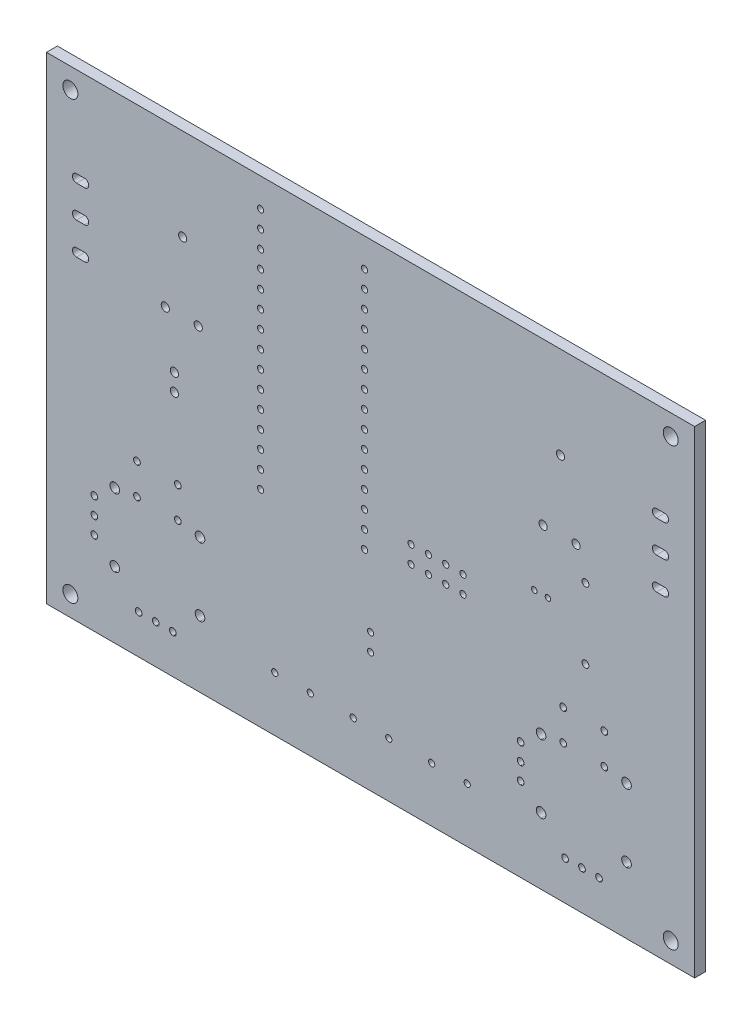
SolidWorks part; units mm, degrees
material "Copper"
ref_plane "Front" through (0, 0, 0) normal (0, 0, 1) x (1, 0, 0)
ref_plane "Top" through (0, 0, 0) normal (0, 1, 0) x (1, 0, 0)
ref_plane "Right" through (0, 0, 0) normal (1, 0, 0) x (0, 0, -1)
sketch "Sketch1" plane through (0, 0, 0) normal (0, 0, 1) x (1, 0, 0)
  line B0 (0, 70) -> (0, 0)
  circle B1 centre (19.9601, 56.5399) radius 1.08
  circle B2 centre (31.38, 60.7) radius 0.4572
  circle B3 centre (31.3799, 60.6999) radius 0.762
  circle B4 centre (31.38, 58.16) radius 0.4572
  circle B5 centre (17.42, 46.38) radius 0.6
  circle B6 centre (17.4201, 46.3799) radius 1.08
  line B7 (95, 70) -> (0, 70)
  line B8 (0, 0) -> (95, 0)
  line B9 (95, 0) -> (95, 70)
  line B10 (6, 57.2) -> (4, 57.2)
  line B11 (4, 57.2) -> (6, 57.2)
  line B12 (6, 55.2) -> (4, 55.2)
  line B13 (4, 55.2) -> (6, 55.2)
  line B14 (5.6, 56.8) -> (4.4, 56.8)
  line B15 (4.4, 56.8) -> (5.6, 56.8)
  line B16 (5.6, 55.6) -> (4.4, 55.6)
  line B17 (4.4, 55.6) -> (5.6, 55.6)
  line B18 (6, 52.5) -> (4, 52.5)
  line B19 (4, 52.5) -> (6, 52.5)
  line B20 (6, 50.5) -> (4, 50.5)
  line B21 (4, 50.5) -> (6, 50.5)
  line B22 (5.6, 52.1) -> (4.4, 52.1)
  line B23 (4.4, 52.1) -> (5.6, 52.1)
  line B24 (5.6, 50.9) -> (4.4, 50.9)
  line B25 (4.4, 50.9) -> (5.6, 50.9)
  line B26 (6, 47.8) -> (4, 47.8)
  line B27 (4, 47.8) -> (6, 47.8)
  line B28 (6, 45.8) -> (4, 45.8)
  line B29 (4, 45.8) -> (6, 45.8)
  line B30 (5.6, 47.4) -> (4.4, 47.4)
  line B31 (4.4, 47.4) -> (5.6, 47.4)
  line B32 (5.6, 46.2) -> (4.4, 46.2)
  line B33 (4.4, 46.2) -> (5.6, 46.2)
  line B34 (91.0001, 57.2) -> (89.0001, 57.2)
  line B35 (89.0001, 57.2) -> (91.0001, 57.2)
  line B36 (91.0001, 55.2) -> (89.0001, 55.2)
  line B37 (89.0001, 55.2) -> (91.0001, 55.2)
  line B38 (90.6, 56.8) -> (89.4, 56.8)
  line B39 (89.4, 56.8) -> (90.6, 56.8)
  line B40 (90.6, 55.6) -> (89.4, 55.6)
  line B41 (89.4, 55.6) -> (90.6, 55.6)
  line B42 (91.0001, 52.5) -> (89.0001, 52.5)
  line B43 (89.0001, 52.5) -> (91.0001, 52.5)
  line B44 (91.0001, 50.5) -> (89.0001, 50.5)
  line B45 (89.0001, 50.5) -> (91.0001, 50.5)
  line B46 (90.6, 52.1) -> (89.4, 52.1)
  line B47 (89.4, 52.1) -> (90.6, 52.1)
  line B48 (90.6, 50.9) -> (89.4, 50.9)
  line B49 (89.4, 50.9) -> (90.6, 50.9)
  line B50 (91.0001, 47.8) -> (89.0001, 47.8)
  line B51 (89.0001, 47.8) -> (91.0001, 47.8)
  line B52 (91.0001, 45.8) -> (89.0001, 45.8)
  line B53 (89.0001, 45.8) -> (91.0001, 45.8)
  line B54 (90.6, 47.4) -> (89.4, 47.4)
  line B55 (89.4, 47.4) -> (90.6, 47.4)
  line B56 (90.6, 46.2) -> (89.4, 46.2)
  line B57 (89.4, 46.2) -> (90.6, 46.2)
  line B58 (19.65, 39.67) -> (19.65, 37.87)
  line B59 (19.65, 37.87) -> (17.85, 37.87)
  line B60 (17.85, 37.87) -> (17.85, 39.67)
  line B61 (17.85, 39.67) -> (19.65, 39.67)
  line B62 (52.6907, 32.4793) -> (54.1893, 32.4793)
  line B63 (54.1893, 32.4793) -> (54.1893, 30.9807)
  line B64 (54.1893, 30.9807) -> (52.6907, 30.9807)
  line B65 (52.6907, 30.9807) -> (52.6907, 32.4793)
  circle B66 centre (19.96, 56.54) radius 0.6
  circle B67 centre (22.246, 46.38) radius 0.6
  circle B68 centre (22.2461, 46.3799) radius 1.08
  circle B69 centre (79.0004, 42.1504) radius 0.5
  circle B70 centre (79.0004, 42.1505) radius 0.762
  circle B71 centre (79.0004, 31.8504) radius 0.5
  circle B72 centre (79.0004, 31.8503) radius 0.762
  circle B73 centre (72.795, 46.38) radius 0.6
  circle B74 centre (72.7951, 46.3799) radius 1.08
  circle B75 centre (75.335, 56.54) radius 0.6
  circle B76 centre (75.3351, 56.5399) radius 1.08
  circle B77 centre (77.621, 46.38) radius 0.6
  circle B78 centre (77.6211, 46.3799) radius 1.08
  circle B79 centre (47.498, 20.143) radius 0.45
  circle B80 centre (47.498, 20.1429) radius 0.8255
  circle B81 centre (47.498, 17.603) radius 0.45
  circle B82 centre (47.498, 17.6029) radius 0.8255
  circle B83 centre (18.75, 36.23) radius 0.6
  circle B84 centre (18.75, 36.23) radius 0.9
  circle B85 centre (33.46, 8) radius 0.4572
  circle B86 centre (33.4599, 8) radius 1
  circle B87 centre (38.667, 8) radius 0.4572
  circle B88 centre (38.6669, 8) radius 1
  circle B89 centre (44.96, 8) radius 0.4572
  circle B90 centre (44.96, 8) radius 1
  circle B91 centre (50.167, 8) radius 0.4572
  circle B92 centre (50.167, 8) radius 1
  circle B93 centre (56.46, 8) radius 0.4572
  circle B94 centre (56.4601, 8) radius 1
  circle B95 centre (61.667, 8) radius 0.4572
  circle B96 centre (61.6671, 8) radius 1
  circle B97 centre (71.5, 37.5) radius 0.4
  circle B98 centre (71.5, 37.5) radius 0.65
  circle B99 centre (73.5, 37.5) radius 0.4
  circle B100 centre (73.5, 37.5) radius 0.65
  circle B101 centre (46.62, 30.22) radius 0.4572
  circle B102 centre (46.6199, 30.2199) radius 0.762
  circle B103 centre (46.62, 32.76) radius 0.4572
  circle B104 centre (46.6199, 32.7599) radius 0.762
  circle B105 centre (46.62, 35.3) radius 0.4572
  circle B106 centre (46.6199, 35.2999) radius 0.762
  circle B107 centre (46.62, 37.84) radius 0.4572
  circle B108 centre (46.6199, 37.8399) radius 0.762
  circle B109 centre (46.62, 40.38) radius 0.4572
  circle B110 centre (46.6199, 40.3799) radius 0.762
  circle B111 centre (46.62, 42.92) radius 0.4572
  circle B112 centre (46.6199, 42.9199) radius 0.762
  circle B113 centre (46.62, 45.46) radius 0.4572
  circle B114 centre (46.6199, 45.4599) radius 0.762
  circle B115 centre (46.62, 48) radius 0.4572
  circle B116 centre (46.6199, 47.9999) radius 0.762
  circle B117 centre (46.62, 50.54) radius 0.4572
  circle B118 centre (46.6199, 50.5399) radius 0.762
  circle B119 centre (46.62, 53.08) radius 0.4572
  circle B120 centre (46.6199, 53.0799) radius 0.762
  circle B121 centre (46.62, 55.62) radius 0.4572
  circle B122 centre (46.6199, 55.6199) radius 0.762
  circle B123 centre (46.62, 58.16) radius 0.4572
  circle B124 centre (46.6199, 58.1599) radius 0.762
  circle B125 centre (46.62, 60.7) radius 0.4572
  circle B126 centre (46.6199, 60.6999) radius 0.762
  circle B127 centre (46.62, 63.24) radius 0.4572
  circle B128 centre (46.6199, 63.2399) radius 0.762
  circle B129 centre (46.62, 65.78) radius 0.4572
  circle B130 centre (46.6199, 65.7799) radius 0.762
  circle B131 centre (31.38, 65.78) radius 0.4572
  circle B132 centre (31.3799, 65.7799) radius 0.762
  circle B133 centre (31.38, 63.24) radius 0.4572
  circle B134 centre (31.3799, 63.2399) radius 0.762
  circle B135 centre (31.3799, 58.1599) radius 0.762
  circle B136 centre (31.38, 55.62) radius 0.4572
  circle B137 centre (31.3799, 55.6199) radius 0.762
  circle B138 centre (31.38, 53.08) radius 0.4572
  circle B139 centre (31.3799, 53.0799) radius 0.762
  circle B140 centre (31.38, 50.54) radius 0.4572
  circle B141 centre (31.3799, 50.5399) radius 0.762
  circle B142 centre (31.38, 48) radius 0.4572
  circle B143 centre (31.3799, 47.9999) radius 0.762
  circle B144 centre (31.38, 45.46) radius 0.4572
  circle B145 centre (31.3799, 45.4599) radius 0.762
  circle B146 centre (31.38, 42.92) radius 0.4572
  circle B147 centre (31.3799, 42.9199) radius 0.762
  circle B148 centre (31.38, 40.38) radius 0.4572
  circle B149 centre (31.3799, 40.3799) radius 0.762
  circle B150 centre (31.38, 37.84) radius 0.4572
  circle B151 centre (31.3799, 37.8399) radius 0.762
  circle B152 centre (31.38, 35.3) radius 0.4572
  circle B153 centre (31.3799, 35.2999) radius 0.762
  circle B154 centre (31.38, 32.76) radius 0.4572
  circle B155 centre (31.3799, 32.7599) radius 0.762
  circle B156 centre (31.38, 30.22) radius 0.4572
  circle B157 centre (31.3799, 30.2199) radius 0.762
  circle B158 centre (8.65, 20.3848) radius 0.6985
  circle B159 centre (8.65, 20.3847) radius 1.143
  circle B160 centre (23.89, 20.3848) radius 0.6985
  circle B161 centre (23.89, 20.3847) radius 1.143
  circle B162 centre (23.89, 7.0752) radius 0.6985
  circle B163 centre (23.89, 7.0751) radius 1.143
  circle B164 centre (8.65, 7.0752) radius 0.6985
  circle B165 centre (8.65, 7.0751) radius 1.143
  circle B166 centre (18.81, 3.57) radius 0.4445
  circle B167 centre (18.81, 3.5699) radius 0.889
  circle B168 centre (16.27, 3.57) radius 0.4445
  circle B169 centre (16.27, 3.5699) radius 0.889
  circle B170 centre (13.73, 3.57) radius 0.4445
  circle B171 centre (13.73, 3.5699) radius 0.889
  circle B172 centre (6.11, 13.73) radius 0.4445
  circle B173 centre (6.11, 13.7299) radius 0.889
  circle B174 centre (6.11, 11.19) radius 0.4445
  circle B175 centre (6.11, 11.1899) radius 0.889
  circle B176 centre (6.11, 16.27) radius 0.4445
  circle B177 centre (6.11, 16.2699) radius 0.889
  circle B178 centre (19.445, 21.35) radius 0.4496
  circle B179 centre (19.445, 21.3499) radius 0.889
  circle B180 centre (13.095, 21.35) radius 0.4496
  circle B181 centre (13.095, 21.3499) radius 0.889
  circle B182 centre (13.095, 26.43) radius 0.4496
  circle B183 centre (13.095, 26.4299) radius 0.889
  circle B184 centre (19.445, 26.43) radius 0.4496
  circle B185 centre (19.445, 26.4299) radius 0.889
  circle B186 centre (71.15, 20.3848) radius 0.6985
  circle B187 centre (71.15, 20.3847) radius 1.143
  circle B188 centre (86.39, 20.3848) radius 0.6985
  circle B189 centre (86.39, 20.3847) radius 1.143
  circle B190 centre (86.39, 7.0752) radius 0.6985
  circle B191 centre (86.39, 7.0751) radius 1.143
  circle B192 centre (71.15, 7.0752) radius 0.6985
  circle B193 centre (71.15, 7.0751) radius 1.143
  circle B194 centre (81.31, 3.57) radius 0.4445
  circle B195 centre (81.31, 3.5699) radius 0.889
  circle B196 centre (78.77, 3.57) radius 0.4445
  circle B197 centre (78.77, 3.5699) radius 0.889
  circle B198 centre (76.23, 3.57) radius 0.4445
  circle B199 centre (76.23, 3.5699) radius 0.889
  circle B200 centre (68.61, 13.73) radius 0.4445
  circle B201 centre (68.61, 13.7299) radius 0.889
  circle B202 centre (68.61, 11.19) radius 0.4445
  circle B203 centre (68.61, 11.1899) radius 0.889
  circle B204 centre (68.61, 16.27) radius 0.4445
  circle B205 centre (68.61, 16.2699) radius 0.889
  circle B206 centre (81.945, 21.35) radius 0.4496
  circle B207 centre (81.945, 21.3499) radius 0.889
  circle B208 centre (75.595, 21.35) radius 0.4496
  circle B209 centre (75.595, 21.3499) radius 0.889
  circle B210 centre (75.595, 26.43) radius 0.4496
  circle B211 centre (75.595, 26.4299) radius 0.889
  circle B212 centre (81.945, 26.43) radius 0.4496
  circle B213 centre (81.945, 26.4299) radius 0.889
  circle B214 centre (55.98, 31.73) radius 0.4572
  circle B215 centre (55.9801, 31.7299) radius 0.7493
  circle B216 centre (58.52, 31.73) radius 0.4572
  circle B217 centre (58.5201, 31.7299) radius 0.7493
  circle B218 centre (61.06, 31.73) radius 0.4572
  circle B219 centre (61.0601, 31.7299) radius 0.7493
  circle B220 centre (61.06, 34.27) radius 0.4572
  circle B221 centre (61.0601, 34.2699) radius 0.7493
  circle B222 centre (58.52, 34.27) radius 0.4572
  circle B223 centre (58.5201, 34.2699) radius 0.7493
  circle B224 centre (55.98, 34.27) radius 0.4572
  circle B225 centre (55.9801, 34.2699) radius 0.7493
  circle B226 centre (53.44, 34.27) radius 0.4572
  circle B227 centre (53.4401, 34.2699) radius 0.7493
  arc B228 (4, 57.2) -> (4, 55.2) centre (4, 56.2) ccw
  arc B229 (6, 55.2) -> (6, 57.2) centre (6, 56.2) ccw
  arc B230 (4.4, 56.8) -> (4.4, 55.6) centre (4.4, 56.2) ccw
  arc B231 (5.6, 55.6) -> (5.6, 56.8) centre (5.6, 56.2) ccw
  arc B232 (4, 52.5) -> (4, 50.5) centre (4, 51.5) ccw
  arc B233 (6, 50.5) -> (6, 52.5) centre (6, 51.5) ccw
  arc B234 (4.4, 52.1) -> (4.4, 50.9) centre (4.4, 51.5) ccw
  arc B235 (5.6, 50.9) -> (5.6, 52.1) centre (5.6, 51.5) ccw
  arc B236 (4, 47.8) -> (4, 45.8) centre (4, 46.8) ccw
  arc B237 (6, 45.8) -> (6, 47.8) centre (6, 46.8) ccw
  arc B238 (4.4, 47.4) -> (4.4, 46.2) centre (4.4, 46.8) ccw
  arc B239 (5.6, 46.2) -> (5.6, 47.4) centre (5.6, 46.8) ccw
  arc B240 (89.0001, 57.2) -> (89.0001, 55.2) centre (89.0001, 56.2) ccw
  arc B241 (91.0001, 55.2) -> (91.0001, 57.2) centre (91.0001, 56.2) ccw
  arc B242 (89.4, 56.8) -> (89.4, 55.6) centre (89.4, 56.2) ccw
  arc B243 (90.6, 55.6) -> (90.6, 56.8) centre (90.6, 56.2) ccw
  arc B244 (89.0001, 52.5) -> (89.0001, 50.5) centre (89.0001, 51.5) ccw
  arc B245 (91.0001, 50.5) -> (91.0001, 52.5) centre (91.0001, 51.5) ccw
  arc B246 (89.4, 52.1) -> (89.4, 50.9) centre (89.4, 51.5) ccw
  arc B247 (90.6, 50.9) -> (90.6, 52.1) centre (90.6, 51.5) ccw
  arc B248 (89.0001, 47.8) -> (89.0001, 45.8) centre (89.0001, 46.8) ccw
  arc B249 (91.0001, 45.8) -> (91.0001, 47.8) centre (91.0001, 46.8) ccw
  arc B250 (89.4, 47.4) -> (89.4, 46.2) centre (89.4, 46.8) ccw
  arc B251 (90.6, 46.2) -> (90.6, 47.4) centre (90.6, 46.8) ccw
  circle B252 centre (18.75, 38.77) radius 0.6
  circle B253 centre (53.44, 31.73) radius 0.4572
  circle B254 centre (3.5001, 3) radius 1.1
  circle B255 centre (91.4999, 3) radius 1.1
  circle B256 centre (91.4999, 66.9998) radius 1.1
  circle B257 centre (3.5001, 66.9998) radius 1.1
sketch_block_instance "based-1"
sketch_block "based"
extrude "Boss-Extrude1" add sketch "Sketch1" along normal mid plane 1.6 contours B9 B7 B0 B8 B257 B256 B255 B254 B249 B52 B248 B50 B245 B44 B244 B42 B241 B36 B240 B34 B237 B28 B236 B26 B233 B20 B232 B18 B229 B12 B228 B10 B227 B225 B223 B221 | B12 B229 B10 B228 B231 B16 B230 B14 | B20 B233 B18 B232 B235 B24 B234 B22 | B28 B237 B26 B236 B239 B32 B238 B30 | B1 B66 | B6 B5 | B68 B67 | B61 B60 B59 B58 B252 | B84 B83 | B183 B182 | B185 B184 | B179 B178 | B181 B180 | B159 B158 | B161 B160 | B173 B172 | B175 B174 | B177 B176 | B165 B164 | B171 B170 | B169 B168 | B167 B166 | B163 B162 | B86 B85 | B88 B87 | B90 B89 | B92 B91 | B96 B95 | B94 B93 | B193 B192 | B203 B202 | B201 B200 | B205 B204 | B199 B198 | B197 B196 | B195 B194 | B191 B190 | B207 B206 | B189 B188 | B187 B186 | B209 B208 | B211 B210 | B213 B212 | B72 B71 | B100 B99 | B98 B97 | B78 B77 | B74 B73 | B70 B69 | B52 B249 B50 B248 B251 B56 B250 B54 | B44 B245 B42 B244 B247 B48 B246 B46 | B36 B241 B34 B240 B243 B40 B242 B38 | B76 B75 | B80 B79 | B82 B81 | B223 B222 | B217 B216 | B215 B214 | B219 B218 | B65 B64 B63 B62 B253 | B225 B224 | B227 B226 | B102 B101 | B104 B103 | B106 B105 | B108 B107 | B110 B109 | B112 B111 | B114 B113 | B116 B115 | B118 B117 | B122 B121 | B120 B119 | B124 B123 | B126 B125 | B128 B127 | B130 B129 | B132 B131 | B135 B4 | B3 B2 | B134 B133 | B137 B136 | B141 B140 | B139 B138 | B143 B142 | B145 B144 | B149 B148 | B147 B146 | B151 B150 | B153 B152 | B155 B154 | B157 B156 | B221 B220 | B158 | B176 | B172 | B174 | B164 | B162 | B178 | B180 | B160 | B182 | B184 | B166 | B168 | B170 | B188 | B186 | B208 | B206 | B212 | B210 | B204 | B200 | B202 | B192 | B198 | B194 | B196 | B190 region at (47.5716, 35.0845, 0) region at (18.9106, 56.5399, 0) region at (30.6395, 60.6999, 0) region at (16.3706, 46.3799, 0) region at (6.9553, 56.2, 0) region at (6.9553, 51.5, 0) region at (6.9553, 46.8, 0) region at (91.9553, 56.2, 0) region at (91.9553, 51.5, 0) region at (91.9553, 46.8, 0) region at (19.6245, 38.77, 0) region at (53.44, 32.4581, 0) region at (21.1966, 46.3799, 0) region at (78.2599, 42.1505, 0) region at (78.2599, 31.8503, 0) region at (71.7457, 46.3799, 0) region at (74.2857, 56.5399, 0) region at (76.5717, 46.3799, 0) region at (46.6958, 20.1429, 0) region at (46.6958, 17.6029, 0) region at (17.8755, 36.23, 0) region at (32.4882, 8, 0) region at (37.6952, 8, 0) region at (43.9883, 8, 0) region at (49.1953, 8, 0) region at (55.4884, 8, 0) region at (60.6954, 8, 0) region at (70.8684, 37.5, 0) region at (72.8684, 37.5, 0) region at (45.8795, 30.2199, 0) region at (45.8795, 32.7599, 0) region at (45.8795, 35.2999, 0) region at (45.8795, 37.8399, 0) region at (45.8795, 40.3799, 0) region at (45.8795, 42.9199, 0) region at (45.8795, 45.4599, 0) region at (45.8795, 47.9999, 0) region at (45.8795, 50.5399, 0) region at (45.8795, 53.0799, 0) region at (45.8795, 55.6199, 0) region at (45.8795, 58.1599, 0) region at (45.8795, 60.6999, 0) region at (45.8795, 63.2399, 0) region at (45.8795, 65.7799, 0) region at (30.6395, 65.7799, 0) region at (30.6395, 63.2399, 0) region at (30.6395, 58.1599, 0) region at (30.6395, 55.6199, 0) region at (30.6395, 53.0799, 0) region at (30.6395, 50.5399, 0) region at (30.6395, 47.9999, 0) region at (30.6395, 45.4599, 0) region at (30.6395, 42.9199, 0) region at (30.6395, 40.3799, 0) region at (30.6395, 37.8399, 0) region at (30.6395, 35.2999, 0) region at (30.6395, 32.7599, 0) region at (30.6395, 30.2199, 0) region at (8.65, 20.3848, 0) region at (7.5393, 20.3847, 0)
sketch "Sketch4" plane through (0, 0, 0.8) normal (0, 0, 1) x (1, 0, 0)
  line B0 (0, 69.9911) -> (0, 0)
  line B1 (0, 0) -> (95.0031, 0)
  line B2 (95.0031, 0) -> (95.0031, 69.9911)
  line B3 (95.0031, 69.9911) -> (0, 69.9911)
  spline B4 degree 3 poles (10.0189, 18.4856) (9.337, 18.4856) (8.7842, 19.0384) (8.7842, 20.4022) (9.337, 20.955) (10.0189, 20.955) knots 2 2 2 2 3 3 4 4 4 4
  spline B5 degree 3 poles (10.0189, 20.955) (10.7008, 20.955) (11.2536, 20.4022) (11.2536, 19.0384) (10.7008, 18.4856) (10.0189, 18.4856) knots 0 0 0 0 1 1 2 2 2 2
  spline B6 degree 3 poles (10.0189, 18.4856) (9.337, 18.4856) (8.7842, 19.0384) (8.7842, 20.4022) (9.337, 20.955) (10.0189, 20.955) knots 2 2 2 2 3 3 4 4 4 4
  spline B7 degree 3 poles (10.0189, 20.955) (10.7008, 20.955) (11.2536, 20.4022) (11.2536, 19.0384) (10.7008, 18.4856) (10.0189, 18.4856) knots 0 0 0 0 1 1 2 2 2 2
  spline B8 degree 3 poles (10.0189, 19.0147) (9.6292, 19.0147) (9.3133, 19.3306) (9.3133, 20.1099) (9.6292, 20.4258) (10.0189, 20.4258) knots 2 2 2 2 3 3 4 4 4 4
  spline B9 degree 3 poles (10.0189, 20.4258) (10.4086, 20.4258) (10.7244, 20.1099) (10.7244, 19.3306) (10.4086, 19.0147) (10.0189, 19.0147) knots 0 0 0 0 1 1 2 2 2 2
  spline B10 degree 3 poles (10.0189, 19.0147) (9.6292, 19.0147) (9.3133, 19.3306) (9.3133, 20.1099) (9.6292, 20.4258) (10.0189, 20.4258) knots 2 2 2 2 3 3 4 4 4 4
  spline B11 degree 3 poles (10.0189, 20.4258) (10.4086, 20.4258) (10.7244, 20.1099) (10.7244, 19.3306) (10.4086, 19.0147) (10.0189, 19.0147) knots 0 0 0 0 1 1 2 2 2 2
  spline B12 degree 3 poles (22.5072, 18.4856) (21.8253, 18.4856) (21.2725, 19.0384) (21.2725, 20.4022) (21.8253, 20.955) (22.5072, 20.955) knots 2 2 2 2 3 3 4 4 4 4
  spline B13 degree 3 poles (22.5072, 20.955) (23.1891, 20.955) (23.7419, 20.4022) (23.7419, 19.0384) (23.1891, 18.4856) (22.5072, 18.4856) knots 0 0 0 0 1 1 2 2 2 2
  spline B14 degree 3 poles (22.5072, 18.4856) (21.8253, 18.4856) (21.2725, 19.0384) (21.2725, 20.4022) (21.8253, 20.955) (22.5072, 20.955) knots 2 2 2 2 3 3 4 4 4 4
  spline B15 degree 3 poles (22.5072, 20.955) (23.1891, 20.955) (23.7419, 20.4022) (23.7419, 19.0384) (23.1891, 18.4856) (22.5072, 18.4856) knots 0 0 0 0 1 1 2 2 2 2
  spline B16 degree 3 poles (22.5072, 19.0147) (22.1176, 19.0147) (21.8017, 19.3306) (21.8017, 20.1099) (22.1176, 20.4258) (22.5072, 20.4258) knots 2 2 2 2 3 3 4 4 4 4
  spline B17 degree 3 poles (22.5072, 20.4258) (22.8969, 20.4258) (23.2128, 20.1099) (23.2128, 19.3306) (22.8969, 19.0147) (22.5072, 19.0147) knots 0 0 0 0 1 1 2 2 2 2
  spline B18 degree 3 poles (22.5072, 19.0147) (22.1176, 19.0147) (21.8017, 19.3306) (21.8017, 20.1099) (22.1176, 20.4258) (22.5072, 20.4258) knots 2 2 2 2 3 3 4 4 4 4
  spline B19 degree 3 poles (22.5072, 20.4258) (22.8969, 20.4258) (23.2128, 20.1099) (23.2128, 19.3306) (22.8969, 19.0147) (22.5072, 19.0147) knots 0 0 0 0 1 1 2 2 2 2
  spline B20 degree 3 poles (22.5072, 8.5019) (21.8253, 8.5019) (21.2725, 9.0547) (21.2725, 10.4186) (21.8253, 10.9714) (22.5072, 10.9714) knots 2 2 2 2 3 3 4 4 4 4
  spline B21 degree 3 poles (22.5072, 10.9714) (23.1891, 10.9714) (23.7419, 10.4186) (23.7419, 9.0547) (23.1891, 8.5019) (22.5072, 8.5019) knots 0 0 0 0 1 1 2 2 2 2
  spline B22 degree 3 poles (22.5072, 8.5019) (21.8253, 8.5019) (21.2725, 9.0547) (21.2725, 10.4186) (21.8253, 10.9714) (22.5072, 10.9714) knots 2 2 2 2 3 3 4 4 4 4
  spline B23 degree 3 poles (22.5072, 10.9714) (23.1891, 10.9714) (23.7419, 10.4186) (23.7419, 9.0547) (23.1891, 8.5019) (22.5072, 8.5019) knots 0 0 0 0 1 1 2 2 2 2
  spline B24 degree 3 poles (22.5072, 9.0311) (22.1176, 9.0311) (21.8017, 9.347) (21.8017, 10.1263) (22.1176, 10.4422) (22.5072, 10.4422) knots 2 2 2 2 3 3 4 4 4 4
  spline B25 degree 3 poles (22.5072, 10.4422) (22.8969, 10.4422) (23.2128, 10.1263) (23.2128, 9.347) (22.8969, 9.0311) (22.5072, 9.0311) knots 0 0 0 0 1 1 2 2 2 2
  spline B26 degree 3 poles (22.5072, 9.0311) (22.1176, 9.0311) (21.8017, 9.347) (21.8017, 10.1263) (22.1176, 10.4422) (22.5072, 10.4422) knots 2 2 2 2 3 3 4 4 4 4
  spline B27 degree 3 poles (22.5072, 10.4422) (22.8969, 10.4422) (23.2128, 10.1263) (23.2128, 9.347) (22.8969, 9.0311) (22.5072, 9.0311) knots 0 0 0 0 1 1 2 2 2 2
  spline B28 degree 3 poles (10.0189, 8.5019) (9.337, 8.5019) (8.7842, 9.0547) (8.7842, 10.4186) (9.337, 10.9714) (10.0189, 10.9714) knots 2 2 2 2 3 3 4 4 4 4
  spline B29 degree 3 poles (10.0189, 10.9714) (10.7008, 10.9714) (11.2536, 10.4186) (11.2536, 9.0547) (10.7008, 8.5019) (10.0189, 8.5019) knots 0 0 0 0 1 1 2 2 2 2
  spline B30 degree 3 poles (10.0189, 8.5019) (9.337, 8.5019) (8.7842, 9.0547) (8.7842, 10.4186) (9.337, 10.9714) (10.0189, 10.9714) knots 2 2 2 2 3 3 4 4 4 4
  spline B31 degree 3 poles (10.0189, 10.9714) (10.7008, 10.9714) (11.2536, 10.4186) (11.2536, 9.0547) (10.7008, 8.5019) (10.0189, 8.5019) knots 0 0 0 0 1 1 2 2 2 2
  spline B32 degree 3 poles (10.0189, 9.0311) (9.6292, 9.0311) (9.3133, 9.347) (9.3133, 10.1263) (9.6292, 10.4422) (10.0189, 10.4422) knots 2 2 2 2 3 3 4 4 4 4
  spline B33 degree 3 poles (10.0189, 10.4422) (10.4086, 10.4422) (10.7244, 10.1263) (10.7244, 9.347) (10.4086, 9.0311) (10.0189, 9.0311) knots 0 0 0 0 1 1 2 2 2 2
  spline B34 degree 3 poles (10.0189, 9.0311) (9.6292, 9.0311) (9.3133, 9.347) (9.3133, 10.1263) (9.6292, 10.4422) (10.0189, 10.4422) knots 2 2 2 2 3 3 4 4 4 4
  spline B35 degree 3 poles (10.0189, 10.4422) (10.4086, 10.4422) (10.7244, 10.1263) (10.7244, 9.347) (10.4086, 9.0311) (10.0189, 9.0311) knots 0 0 0 0 1 1 2 2 2 2
  spline B36 degree 3 poles (18.5208, 4.7272) (17.9753, 4.7272) (17.5331, 5.1695) (17.5331, 6.2605) (17.9753, 6.7028) (18.5208, 6.7028) knots 2 2 2 2 3 3 4 4 4 4
  spline B37 degree 3 poles (18.5208, 6.7028) (19.0664, 6.7028) (19.5086, 6.2605) (19.5086, 5.1695) (19.0664, 4.7272) (18.5208, 4.7272) knots 0 0 0 0 1 1 2 2 2 2
  spline B38 degree 3 poles (18.5208, 4.7272) (17.9753, 4.7272) (17.5331, 5.1695) (17.5331, 6.2605) (17.9753, 6.7028) (18.5208, 6.7028) knots 2 2 2 2 3 3 4 4 4 4
  spline B39 degree 3 poles (18.5208, 6.7028) (19.0664, 6.7028) (19.5086, 6.2605) (19.5086, 5.1695) (19.0664, 4.7272) (18.5208, 4.7272) knots 0 0 0 0 1 1 2 2 2 2
  spline B40 degree 3 poles (18.5208, 5.2211) (18.2481, 5.2211) (18.0269, 5.4422) (18.0269, 5.9878) (18.2481, 6.2089) (18.5208, 6.2089) knots 2 2 2 2 3 3 4 4 4 4
  spline B41 degree 3 poles (18.5208, 6.2089) (18.7936, 6.2089) (19.0147, 5.9878) (19.0147, 5.4422) (18.7936, 5.2211) (18.5208, 5.2211) knots 0 0 0 0 1 1 2 2 2 2
  spline B42 degree 3 poles (18.5208, 5.2211) (18.2481, 5.2211) (18.0269, 5.4422) (18.0269, 5.9878) (18.2481, 6.2089) (18.5208, 6.2089) knots 2 2 2 2 3 3 4 4 4 4
  spline B43 degree 3 poles (18.5208, 6.2089) (18.7936, 6.2089) (19.0147, 5.9878) (19.0147, 5.4422) (18.7936, 5.2211) (18.5208, 5.2211) knots 0 0 0 0 1 1 2 2 2 2
  spline B44 degree 3 poles (16.0161, 4.7272) (15.4706, 4.7272) (15.0283, 5.1695) (15.0283, 6.2605) (15.4706, 6.7028) (16.0161, 6.7028) knots 2 2 2 2 3 3 4 4 4 4
  spline B45 degree 3 poles (16.0161, 6.7028) (16.5616, 6.7028) (17.0039, 6.2605) (17.0039, 5.1695) (16.5616, 4.7272) (16.0161, 4.7272) knots 0 0 0 0 1 1 2 2 2 2
  spline B46 degree 3 poles (16.0161, 4.7272) (15.4706, 4.7272) (15.0283, 5.1695) (15.0283, 6.2605) (15.4706, 6.7028) (16.0161, 6.7028) knots 2 2 2 2 3 3 4 4 4 4
  spline B47 degree 3 poles (16.0161, 6.7028) (16.5616, 6.7028) (17.0039, 6.2605) (17.0039, 5.1695) (16.5616, 4.7272) (16.0161, 4.7272) knots 0 0 0 0 1 1 2 2 2 2
  spline B48 degree 3 poles (16.0161, 5.2211) (15.7433, 5.2211) (15.5222, 5.4422) (15.5222, 5.9878) (15.7433, 6.2089) (16.0161, 6.2089) knots 2 2 2 2 3 3 4 4 4 4
  spline B49 degree 3 poles (16.0161, 6.2089) (16.2889, 6.2089) (16.51, 5.9878) (16.51, 5.4422) (16.2889, 5.2211) (16.0161, 5.2211) knots 0 0 0 0 1 1 2 2 2 2
  spline B50 degree 3 poles (16.0161, 5.2211) (15.7433, 5.2211) (15.5222, 5.4422) (15.5222, 5.9878) (15.7433, 6.2089) (16.0161, 6.2089) knots 2 2 2 2 3 3 4 4 4 4
  spline B51 degree 3 poles (16.0161, 6.2089) (16.2889, 6.2089) (16.51, 5.9878) (16.51, 5.4422) (16.2889, 5.2211) (16.0161, 5.2211) knots 0 0 0 0 1 1 2 2 2 2
  spline B52 degree 3 poles (13.5114, 4.7272) (12.9659, 4.7272) (12.5236, 5.1695) (12.5236, 6.2605) (12.9659, 6.7028) (13.5114, 6.7028) knots 2 2 2 2 3 3 4 4 4 4
  spline B53 degree 3 poles (13.5114, 6.7028) (14.0569, 6.7028) (14.4992, 6.2605) (14.4992, 5.1695) (14.0569, 4.7272) (13.5114, 4.7272) knots 0 0 0 0 1 1 2 2 2 2
  spline B54 degree 3 poles (13.5114, 4.7272) (12.9659, 4.7272) (12.5236, 5.1695) (12.5236, 6.2605) (12.9659, 6.7028) (13.5114, 6.7028) knots 2 2 2 2 3 3 4 4 4 4
  spline B55 degree 3 poles (13.5114, 6.7028) (14.0569, 6.7028) (14.4992, 6.2605) (14.4992, 5.1695) (14.0569, 4.7272) (13.5114, 4.7272) knots 0 0 0 0 1 1 2 2 2 2
  spline B56 degree 3 poles (13.5114, 5.2211) (13.2386, 5.2211) (13.0175, 5.4422) (13.0175, 5.9878) (13.2386, 6.2089) (13.5114, 6.2089) knots 2 2 2 2 3 3 4 4 4 4
  spline B57 degree 3 poles (13.5114, 6.2089) (13.7842, 6.2089) (14.0053, 5.9878) (14.0053, 5.4422) (13.7842, 5.2211) (13.5114, 5.2211) knots 0 0 0 0 1 1 2 2 2 2
  spline B58 degree 3 poles (13.5114, 5.2211) (13.2386, 5.2211) (13.0175, 5.4422) (13.0175, 5.9878) (13.2386, 6.2089) (13.5114, 6.2089) knots 2 2 2 2 3 3 4 4 4 4
  spline B59 degree 3 poles (13.5114, 6.2089) (13.7842, 6.2089) (14.0053, 5.9878) (14.0053, 5.4422) (13.7842, 5.2211) (13.5114, 5.2211) knots 0 0 0 0 1 1 2 2 2 2
  spline B60 degree 3 poles (7.0203, 13.7231) (6.4747, 13.7231) (6.0325, 14.1653) (6.0325, 15.2564) (6.4747, 15.6986) (7.0203, 15.6986) knots 2 2 2 2 3 3 4 4 4 4
  spline B61 degree 3 poles (7.0203, 15.6986) (7.5658, 15.6986) (8.008, 15.2564) (8.008, 14.1653) (7.5658, 13.7231) (7.0203, 13.7231) knots 0 0 0 0 1 1 2 2 2 2
  spline B62 degree 3 poles (7.0203, 13.7231) (6.4747, 13.7231) (6.0325, 14.1653) (6.0325, 15.2564) (6.4747, 15.6986) (7.0203, 15.6986) knots 2 2 2 2 3 3 4 4 4 4
  spline B63 degree 3 poles (7.0203, 15.6986) (7.5658, 15.6986) (8.008, 15.2564) (8.008, 14.1653) (7.5658, 13.7231) (7.0203, 13.7231) knots 0 0 0 0 1 1 2 2 2 2
  spline B64 degree 3 poles (7.0203, 14.2169) (6.7475, 14.2169) (6.5264, 14.4381) (6.5264, 14.9836) (6.7475, 15.2047) (7.0203, 15.2047) knots 2 2 2 2 3 3 4 4 4 4
  spline B65 degree 3 poles (7.0203, 15.2047) (7.293, 15.2047) (7.5142, 14.9836) (7.5142, 14.4381) (7.293, 14.2169) (7.0203, 14.2169) knots 0 0 0 0 1 1 2 2 2 2
  spline B66 degree 3 poles (7.0203, 14.2169) (6.7475, 14.2169) (6.5264, 14.4381) (6.5264, 14.9836) (6.7475, 15.2047) (7.0203, 15.2047) knots 2 2 2 2 3 3 4 4 4 4
  spline B67 degree 3 poles (7.0203, 15.2047) (7.293, 15.2047) (7.5142, 14.9836) (7.5142, 14.4381) (7.293, 14.2169) (7.0203, 14.2169) knots 0 0 0 0 1 1 2 2 2 2
  spline B68 degree 3 poles (7.0203, 11.2536) (6.4747, 11.2536) (6.0325, 11.6959) (6.0325, 12.7869) (6.4747, 13.2292) (7.0203, 13.2292) knots 2 2 2 2 3 3 4 4 4 4
  spline B69 degree 3 poles (7.0203, 13.2292) (7.5658, 13.2292) (8.008, 12.7869) (8.008, 11.6959) (7.5658, 11.2536) (7.0203, 11.2536) knots 0 0 0 0 1 1 2 2 2 2
  spline B70 degree 3 poles (7.0203, 11.2536) (6.4747, 11.2536) (6.0325, 11.6959) (6.0325, 12.7869) (6.4747, 13.2292) (7.0203, 13.2292) knots 2 2 2 2 3 3 4 4 4 4
  spline B71 degree 3 poles (7.0203, 13.2292) (7.5658, 13.2292) (8.008, 12.7869) (8.008, 11.6959) (7.5658, 11.2536) (7.0203, 11.2536) knots 0 0 0 0 1 1 2 2 2 2
  spline B72 degree 3 poles (7.0203, 11.7475) (6.7475, 11.7475) (6.5264, 11.9686) (6.5264, 12.5141) (6.7475, 12.7353) (7.0203, 12.7353) knots 2 2 2 2 3 3 4 4 4 4
  spline B73 degree 3 poles (7.0203, 12.7353) (7.293, 12.7353) (7.5142, 12.5141) (7.5142, 11.9686) (7.293, 11.7475) (7.0203, 11.7475) knots 0 0 0 0 1 1 2 2 2 2
  spline B74 degree 3 poles (7.0203, 11.7475) (6.7475, 11.7475) (6.5264, 11.9686) (6.5264, 12.5141) (6.7475, 12.7353) (7.0203, 12.7353) knots 2 2 2 2 3 3 4 4 4 4
  spline B75 degree 3 poles (7.0203, 12.7353) (7.293, 12.7353) (7.5142, 12.5141) (7.5142, 11.9686) (7.293, 11.7475) (7.0203, 11.7475) knots 0 0 0 0 1 1 2 2 2 2
  spline B76 degree 3 poles (7.0203, 16.2278) (6.4747, 16.2278) (6.0325, 16.67) (6.0325, 17.7611) (6.4747, 18.2033) (7.0203, 18.2033) knots 2 2 2 2 3 3 4 4 4 4
  spline B77 degree 3 poles (7.0203, 18.2033) (7.5658, 18.2033) (8.008, 17.7611) (8.008, 16.67) (7.5658, 16.2278) (7.0203, 16.2278) knots 0 0 0 0 1 1 2 2 2 2
  spline B78 degree 3 poles (7.0203, 16.2278) (6.4747, 16.2278) (6.0325, 16.67) (6.0325, 17.7611) (6.4747, 18.2033) (7.0203, 18.2033) knots 2 2 2 2 3 3 4 4 4 4
  spline B79 degree 3 poles (7.0203, 18.2033) (7.5658, 18.2033) (8.008, 17.7611) (8.008, 16.67) (7.5658, 16.2278) (7.0203, 16.2278) knots 0 0 0 0 1 1 2 2 2 2
  spline B80 degree 3 poles (7.0203, 16.7217) (6.7475, 16.7217) (6.5264, 16.9428) (6.5264, 17.4883) (6.7475, 17.7094) (7.0203, 17.7094) knots 2 2 2 2 3 3 4 4 4 4
  spline B81 degree 3 poles (7.0203, 17.7094) (7.293, 17.7094) (7.5142, 17.4883) (7.5142, 16.9428) (7.293, 16.7217) (7.0203, 16.7217) knots 0 0 0 0 1 1 2 2 2 2
  spline B82 degree 3 poles (7.0203, 16.7217) (6.7475, 16.7217) (6.5264, 16.9428) (6.5264, 17.4883) (6.7475, 17.7094) (7.0203, 17.7094) knots 2 2 2 2 3 3 4 4 4 4
  spline B83 degree 3 poles (7.0203, 17.7094) (7.293, 17.7094) (7.5142, 17.4883) (7.5142, 16.9428) (7.293, 16.7217) (7.0203, 16.7217) knots 0 0 0 0 1 1 2 2 2 2
  spline B84 degree 3 poles (19.2617, 19.2264) (18.7161, 19.2264) (18.2739, 19.6686) (18.2739, 20.7597) (18.7161, 21.2019) (19.2617, 21.2019) knots 2 2 2 2 3 3 4 4 4 4
  spline B85 degree 3 poles (19.2617, 21.2019) (19.8072, 21.2019) (20.2494, 20.7597) (20.2494, 19.6686) (19.8072, 19.2264) (19.2617, 19.2264) knots 0 0 0 0 1 1 2 2 2 2
  spline B86 degree 3 poles (19.2617, 19.2264) (18.7161, 19.2264) (18.2739, 19.6686) (18.2739, 20.7597) (18.7161, 21.2019) (19.2617, 21.2019) knots 2 2 2 2 3 3 4 4 4 4
  spline B87 degree 3 poles (19.2617, 21.2019) (19.8072, 21.2019) (20.2494, 20.7597) (20.2494, 19.6686) (19.8072, 19.2264) (19.2617, 19.2264) knots 0 0 0 0 1 1 2 2 2 2
  spline B88 degree 3 poles (19.2617, 19.7203) (18.9889, 19.7203) (18.7678, 19.9414) (18.7678, 20.4869) (18.9889, 20.708) (19.2617, 20.708) knots 2 2 2 2 3 3 4 4 4 4
  spline B89 degree 3 poles (19.2617, 20.708) (19.5344, 20.708) (19.7556, 20.4869) (19.7556, 19.9414) (19.5344, 19.7203) (19.2617, 19.7203) knots 0 0 0 0 1 1 2 2 2 2
  spline B90 degree 3 poles (19.2617, 19.7203) (18.9889, 19.7203) (18.7678, 19.9414) (18.7678, 20.4869) (18.9889, 20.708) (19.2617, 20.708) knots 2 2 2 2 3 3 4 4 4 4
  spline B91 degree 3 poles (19.2617, 20.708) (19.5344, 20.708) (19.7556, 20.4869) (19.7556, 19.9414) (19.5344, 19.7203) (19.2617, 19.7203) knots 0 0 0 0 1 1 2 2 2 2
  spline B92 degree 3 poles (13.2644, 19.2264) (12.7189, 19.2264) (12.2767, 19.6686) (12.2767, 20.7597) (12.7189, 21.2019) (13.2644, 21.2019) knots 2 2 2 2 3 3 4 4 4 4
  spline B93 degree 3 poles (13.2644, 21.2019) (13.81, 21.2019) (14.2522, 20.7597) (14.2522, 19.6686) (13.81, 19.2264) (13.2644, 19.2264) knots 0 0 0 0 1 1 2 2 2 2
  spline B94 degree 3 poles (13.2644, 19.2264) (12.7189, 19.2264) (12.2767, 19.6686) (12.2767, 20.7597) (12.7189, 21.2019) (13.2644, 21.2019) knots 2 2 2 2 3 3 4 4 4 4
  spline B95 degree 3 poles (13.2644, 21.2019) (13.81, 21.2019) (14.2522, 20.7597) (14.2522, 19.6686) (13.81, 19.2264) (13.2644, 19.2264) knots 0 0 0 0 1 1 2 2 2 2
  spline B96 degree 3 poles (13.2644, 19.7203) (12.9917, 19.7203) (12.7706, 19.9414) (12.7706, 20.4869) (12.9917, 20.708) (13.2644, 20.708) knots 2 2 2 2 3 3 4 4 4 4
  spline B97 degree 3 poles (13.2644, 20.708) (13.5372, 20.708) (13.7583, 20.4869) (13.7583, 19.9414) (13.5372, 19.7203) (13.2644, 19.7203) knots 0 0 0 0 1 1 2 2 2 2
  spline B98 degree 3 poles (13.2644, 19.7203) (12.9917, 19.7203) (12.7706, 19.9414) (12.7706, 20.4869) (12.9917, 20.708) (13.2644, 20.708) knots 2 2 2 2 3 3 4 4 4 4
  spline B99 degree 3 poles (13.2644, 20.708) (13.5372, 20.708) (13.7583, 20.4869) (13.7583, 19.9414) (13.5372, 19.7203) (13.2644, 19.7203) knots 0 0 0 0 1 1 2 2 2 2
  spline B100 degree 3 poles (13.2644, 23.7419) (12.7189, 23.7419) (12.2767, 24.1842) (12.2767, 25.2752) (12.7189, 25.7175) (13.2644, 25.7175) knots 2 2 2 2 3 3 4 4 4 4
  spline B101 degree 3 poles (13.2644, 25.7175) (13.81, 25.7175) (14.2522, 25.2752) (14.2522, 24.1842) (13.81, 23.7419) (13.2644, 23.7419) knots 0 0 0 0 1 1 2 2 2 2
  spline B102 degree 3 poles (13.2644, 23.7419) (12.7189, 23.7419) (12.2767, 24.1842) (12.2767, 25.2752) (12.7189, 25.7175) (13.2644, 25.7175) knots 2 2 2 2 3 3 4 4 4 4
  spline B103 degree 3 poles (13.2644, 25.7175) (13.81, 25.7175) (14.2522, 25.2752) (14.2522, 24.1842) (13.81, 23.7419) (13.2644, 23.7419) knots 0 0 0 0 1 1 2 2 2 2
  spline B104 degree 3 poles (13.2644, 24.2358) (12.9917, 24.2358) (12.7706, 24.4569) (12.7706, 25.0025) (12.9917, 25.2236) (13.2644, 25.2236) knots 2 2 2 2 3 3 4 4 4 4
  spline B105 degree 3 poles (13.2644, 25.2236) (13.5372, 25.2236) (13.7583, 25.0025) (13.7583, 24.4569) (13.5372, 24.2358) (13.2644, 24.2358) knots 0 0 0 0 1 1 2 2 2 2
  spline B106 degree 3 poles (13.2644, 24.2358) (12.9917, 24.2358) (12.7706, 24.4569) (12.7706, 25.0025) (12.9917, 25.2236) (13.2644, 25.2236) knots 2 2 2 2 3 3 4 4 4 4
  spline B107 degree 3 poles (13.2644, 25.2236) (13.5372, 25.2236) (13.7583, 25.0025) (13.7583, 24.4569) (13.5372, 24.2358) (13.2644, 24.2358) knots 0 0 0 0 1 1 2 2 2 2
  spline B108 degree 3 poles (19.2617, 23.7419) (18.7161, 23.7419) (18.2739, 24.1842) (18.2739, 25.2752) (18.7161, 25.7175) (19.2617, 25.7175) knots 2 2 2 2 3 3 4 4 4 4
  spline B109 degree 3 poles (19.2617, 25.7175) (19.8072, 25.7175) (20.2494, 25.2752) (20.2494, 24.1842) (19.8072, 23.7419) (19.2617, 23.7419) knots 0 0 0 0 1 1 2 2 2 2
  spline B110 degree 3 poles (19.2617, 23.7419) (18.7161, 23.7419) (18.2739, 24.1842) (18.2739, 25.2752) (18.7161, 25.7175) (19.2617, 25.7175) knots 2 2 2 2 3 3 4 4 4 4
  spline B111 degree 3 poles (19.2617, 25.7175) (19.8072, 25.7175) (20.2494, 25.2752) (20.2494, 24.1842) (19.8072, 23.7419) (19.2617, 23.7419) knots 0 0 0 0 1 1 2 2 2 2
  spline B112 degree 3 poles (19.2617, 24.2358) (18.9889, 24.2358) (18.7678, 24.4569) (18.7678, 25.0025) (18.9889, 25.2236) (19.2617, 25.2236) knots 2 2 2 2 3 3 4 4 4 4
  spline B113 degree 3 poles (19.2617, 25.2236) (19.5344, 25.2236) (19.7556, 25.0025) (19.7556, 24.4569) (19.5344, 24.2358) (19.2617, 24.2358) knots 0 0 0 0 1 1 2 2 2 2
  spline B114 degree 3 poles (19.2617, 24.2358) (18.9889, 24.2358) (18.7678, 24.4569) (18.7678, 25.0025) (18.9889, 25.2236) (19.2617, 25.2236) knots 2 2 2 2 3 3 4 4 4 4
  spline B115 degree 3 poles (19.2617, 25.2236) (19.5344, 25.2236) (19.7556, 25.0025) (19.7556, 24.4569) (19.5344, 24.2358) (19.2617, 24.2358) knots 0 0 0 0 1 1 2 2 2 2
  spline B116 degree 3 poles (72.4958, 18.4856) (71.8139, 18.4856) (71.2611, 19.0384) (71.2611, 20.4022) (71.8139, 20.955) (72.4958, 20.955) knots 2 2 2 2 3 3 4 4 4 4
  spline B117 degree 3 poles (72.4958, 20.955) (73.1778, 20.955) (73.7306, 20.4022) (73.7306, 19.0384) (73.1778, 18.4856) (72.4958, 18.4856) knots 0 0 0 0 1 1 2 2 2 2
  spline B118 degree 3 poles (72.4958, 18.4856) (71.8139, 18.4856) (71.2611, 19.0384) (71.2611, 20.4022) (71.8139, 20.955) (72.4958, 20.955) knots 2 2 2 2 3 3 4 4 4 4
  spline B119 degree 3 poles (72.4958, 20.955) (73.1778, 20.955) (73.7306, 20.4022) (73.7306, 19.0384) (73.1778, 18.4856) (72.4958, 18.4856) knots 0 0 0 0 1 1 2 2 2 2
  spline B120 degree 3 poles (72.4958, 19.0147) (72.1062, 19.0147) (71.7903, 19.3306) (71.7903, 20.1099) (72.1062, 20.4258) (72.4958, 20.4258) knots 2 2 2 2 3 3 4 4 4 4
  spline B121 degree 3 poles (72.4958, 20.4258) (72.8855, 20.4258) (73.2014, 20.1099) (73.2014, 19.3306) (72.8855, 19.0147) (72.4958, 19.0147) knots 0 0 0 0 1 1 2 2 2 2
  spline B122 degree 3 poles (72.4958, 19.0147) (72.1062, 19.0147) (71.7903, 19.3306) (71.7903, 20.1099) (72.1062, 20.4258) (72.4958, 20.4258) knots 2 2 2 2 3 3 4 4 4 4
  spline B123 degree 3 poles (72.4958, 20.4258) (72.8855, 20.4258) (73.2014, 20.1099) (73.2014, 19.3306) (72.8855, 19.0147) (72.4958, 19.0147) knots 0 0 0 0 1 1 2 2 2 2
  spline B124 degree 3 poles (85.0194, 18.4856) (84.3375, 18.4856) (83.7847, 19.0384) (83.7847, 20.4022) (84.3375, 20.955) (85.0194, 20.955) knots 2 2 2 2 3 3 4 4 4 4
  spline B125 degree 3 poles (85.0194, 20.955) (85.7014, 20.955) (86.2542, 20.4022) (86.2542, 19.0384) (85.7014, 18.4856) (85.0194, 18.4856) knots 0 0 0 0 1 1 2 2 2 2
  spline B126 degree 3 poles (85.0194, 18.4856) (84.3375, 18.4856) (83.7847, 19.0384) (83.7847, 20.4022) (84.3375, 20.955) (85.0194, 20.955) knots 2 2 2 2 3 3 4 4 4 4
  spline B127 degree 3 poles (85.0194, 20.955) (85.7014, 20.955) (86.2542, 20.4022) (86.2542, 19.0384) (85.7014, 18.4856) (85.0194, 18.4856) knots 0 0 0 0 1 1 2 2 2 2
  spline B128 degree 3 poles (85.0194, 19.0147) (84.6298, 19.0147) (84.3139, 19.3306) (84.3139, 20.1099) (84.6298, 20.4258) (85.0194, 20.4258) knots 2 2 2 2 3 3 4 4 4 4
  spline B129 degree 3 poles (85.0194, 20.4258) (85.4091, 20.4258) (85.725, 20.1099) (85.725, 19.3306) (85.4091, 19.0147) (85.0194, 19.0147) knots 0 0 0 0 1 1 2 2 2 2
  spline B130 degree 3 poles (85.0194, 19.0147) (84.6298, 19.0147) (84.3139, 19.3306) (84.3139, 20.1099) (84.6298, 20.4258) (85.0194, 20.4258) knots 2 2 2 2 3 3 4 4 4 4
  spline B131 degree 3 poles (85.0194, 20.4258) (85.4091, 20.4258) (85.725, 20.1099) (85.725, 19.3306) (85.4091, 19.0147) (85.0194, 19.0147) knots 0 0 0 0 1 1 2 2 2 2
  spline B132 degree 3 poles (85.0194, 8.5019) (84.3375, 8.5019) (83.7847, 9.0547) (83.7847, 10.4186) (84.3375, 10.9714) (85.0194, 10.9714) knots 2 2 2 2 3 3 4 4 4 4
  spline B133 degree 3 poles (85.0194, 10.9714) (85.7014, 10.9714) (86.2542, 10.4186) (86.2542, 9.0547) (85.7014, 8.5019) (85.0194, 8.5019) knots 0 0 0 0 1 1 2 2 2 2
  spline B134 degree 3 poles (85.0194, 8.5019) (84.3375, 8.5019) (83.7847, 9.0547) (83.7847, 10.4186) (84.3375, 10.9714) (85.0194, 10.9714) knots 2 2 2 2 3 3 4 4 4 4
  spline B135 degree 3 poles (85.0194, 10.9714) (85.7014, 10.9714) (86.2542, 10.4186) (86.2542, 9.0547) (85.7014, 8.5019) (85.0194, 8.5019) knots 0 0 0 0 1 1 2 2 2 2
  spline B136 degree 3 poles (85.0194, 9.0311) (84.6298, 9.0311) (84.3139, 9.347) (84.3139, 10.1263) (84.6298, 10.4422) (85.0194, 10.4422) knots 2 2 2 2 3 3 4 4 4 4
  spline B137 degree 3 poles (85.0194, 10.4422) (85.4091, 10.4422) (85.725, 10.1263) (85.725, 9.347) (85.4091, 9.0311) (85.0194, 9.0311) knots 0 0 0 0 1 1 2 2 2 2
  spline B138 degree 3 poles (85.0194, 9.0311) (84.6298, 9.0311) (84.3139, 9.347) (84.3139, 10.1263) (84.6298, 10.4422) (85.0194, 10.4422) knots 2 2 2 2 3 3 4 4 4 4
  spline B139 degree 3 poles (85.0194, 10.4422) (85.4091, 10.4422) (85.725, 10.1263) (85.725, 9.347) (85.4091, 9.0311) (85.0194, 9.0311) knots 0 0 0 0 1 1 2 2 2 2
  spline B140 degree 3 poles (72.4958, 8.5019) (71.8139, 8.5019) (71.2611, 9.0547) (71.2611, 10.4186) (71.8139, 10.9714) (72.4958, 10.9714) knots 2 2 2 2 3 3 4 4 4 4
  spline B141 degree 3 poles (72.4958, 10.9714) (73.1778, 10.9714) (73.7306, 10.4186) (73.7306, 9.0547) (73.1778, 8.5019) (72.4958, 8.5019) knots 0 0 0 0 1 1 2 2 2 2
  spline B142 degree 3 poles (72.4958, 8.5019) (71.8139, 8.5019) (71.2611, 9.0547) (71.2611, 10.4186) (71.8139, 10.9714) (72.4958, 10.9714) knots 2 2 2 2 3 3 4 4 4 4
  spline B143 degree 3 poles (72.4958, 10.9714) (73.1778, 10.9714) (73.7306, 10.4186) (73.7306, 9.0547) (73.1778, 8.5019) (72.4958, 8.5019) knots 0 0 0 0 1 1 2 2 2 2
  spline B144 degree 3 poles (72.4958, 9.0311) (72.1062, 9.0311) (71.7903, 9.347) (71.7903, 10.1263) (72.1062, 10.4422) (72.4958, 10.4422) knots 2 2 2 2 3 3 4 4 4 4
  spline B145 degree 3 poles (72.4958, 10.4422) (72.8855, 10.4422) (73.2014, 10.1263) (73.2014, 9.347) (72.8855, 9.0311) (72.4958, 9.0311) knots 0 0 0 0 1 1 2 2 2 2
  spline B146 degree 3 poles (72.4958, 9.0311) (72.1062, 9.0311) (71.7903, 9.347) (71.7903, 10.1263) (72.1062, 10.4422) (72.4958, 10.4422) knots 2 2 2 2 3 3 4 4 4 4
  spline B147 degree 3 poles (72.4958, 10.4422) (72.8855, 10.4422) (73.2014, 10.1263) (73.2014, 9.347) (72.8855, 9.0311) (72.4958, 9.0311) knots 0 0 0 0 1 1 2 2 2 2
  spline B148 degree 3 poles (80.9978, 4.7272) (80.4522, 4.7272) (80.01, 5.1695) (80.01, 6.2605) (80.4522, 6.7028) (80.9978, 6.7028) knots 2 2 2 2 3 3 4 4 4 4
  spline B149 degree 3 poles (80.9978, 6.7028) (81.5433, 6.7028) (81.9856, 6.2605) (81.9856, 5.1695) (81.5433, 4.7272) (80.9978, 4.7272) knots 0 0 0 0 1 1 2 2 2 2
  spline B150 degree 3 poles (80.9978, 4.7272) (80.4522, 4.7272) (80.01, 5.1695) (80.01, 6.2605) (80.4522, 6.7028) (80.9978, 6.7028) knots 2 2 2 2 3 3 4 4 4 4
  spline B151 degree 3 poles (80.9978, 6.7028) (81.5433, 6.7028) (81.9856, 6.2605) (81.9856, 5.1695) (81.5433, 4.7272) (80.9978, 4.7272) knots 0 0 0 0 1 1 2 2 2 2
  spline B152 degree 3 poles (80.9978, 5.2211) (80.725, 5.2211) (80.5039, 5.4422) (80.5039, 5.9878) (80.725, 6.2089) (80.9978, 6.2089) knots 2 2 2 2 3 3 4 4 4 4
  spline B153 degree 3 poles (80.9978, 6.2089) (81.2705, 6.2089) (81.4917, 5.9878) (81.4917, 5.4422) (81.2705, 5.2211) (80.9978, 5.2211) knots 0 0 0 0 1 1 2 2 2 2
  spline B154 degree 3 poles (80.9978, 5.2211) (80.725, 5.2211) (80.5039, 5.4422) (80.5039, 5.9878) (80.725, 6.2089) (80.9978, 6.2089) knots 2 2 2 2 3 3 4 4 4 4
  spline B155 degree 3 poles (80.9978, 6.2089) (81.2705, 6.2089) (81.4917, 5.9878) (81.4917, 5.4422) (81.2705, 5.2211) (80.9978, 5.2211) knots 0 0 0 0 1 1 2 2 2 2
  spline B156 degree 3 poles (78.4931, 4.7272) (77.9475, 4.7272) (77.5053, 5.1695) (77.5053, 6.2605) (77.9475, 6.7028) (78.4931, 6.7028) knots 2 2 2 2 3 3 4 4 4 4
  spline B157 degree 3 poles (78.4931, 6.7028) (79.0386, 6.7028) (79.4808, 6.2605) (79.4808, 5.1695) (79.0386, 4.7272) (78.4931, 4.7272) knots 0 0 0 0 1 1 2 2 2 2
  spline B158 degree 3 poles (78.4931, 4.7272) (77.9475, 4.7272) (77.5053, 5.1695) (77.5053, 6.2605) (77.9475, 6.7028) (78.4931, 6.7028) knots 2 2 2 2 3 3 4 4 4 4
  spline B159 degree 3 poles (78.4931, 6.7028) (79.0386, 6.7028) (79.4808, 6.2605) (79.4808, 5.1695) (79.0386, 4.7272) (78.4931, 4.7272) knots 0 0 0 0 1 1 2 2 2 2
  spline B160 degree 3 poles (78.4931, 5.2211) (78.2203, 5.2211) (77.9992, 5.4422) (77.9992, 5.9878) (78.2203, 6.2089) (78.4931, 6.2089) knots 2 2 2 2 3 3 4 4 4 4
  spline B161 degree 3 poles (78.4931, 6.2089) (78.7658, 6.2089) (78.9869, 5.9878) (78.9869, 5.4422) (78.7658, 5.2211) (78.4931, 5.2211) knots 0 0 0 0 1 1 2 2 2 2
  spline B162 degree 3 poles (78.4931, 5.2211) (78.2203, 5.2211) (77.9992, 5.4422) (77.9992, 5.9878) (78.2203, 6.2089) (78.4931, 6.2089) knots 2 2 2 2 3 3 4 4 4 4
  spline B163 degree 3 poles (78.4931, 6.2089) (78.7658, 6.2089) (78.9869, 5.9878) (78.9869, 5.4422) (78.7658, 5.2211) (78.4931, 5.2211) knots 0 0 0 0 1 1 2 2 2 2
  spline B164 degree 3 poles (76.0236, 4.7272) (75.4781, 4.7272) (75.0358, 5.1695) (75.0358, 6.2605) (75.4781, 6.7028) (76.0236, 6.7028) knots 2 2 2 2 3 3 4 4 4 4
  spline B165 degree 3 poles (76.0236, 6.7028) (76.5691, 6.7028) (77.0114, 6.2605) (77.0114, 5.1695) (76.5691, 4.7272) (76.0236, 4.7272) knots 0 0 0 0 1 1 2 2 2 2
  spline B166 degree 3 poles (76.0236, 4.7272) (75.4781, 4.7272) (75.0358, 5.1695) (75.0358, 6.2605) (75.4781, 6.7028) (76.0236, 6.7028) knots 2 2 2 2 3 3 4 4 4 4
  spline B167 degree 3 poles (76.0236, 6.7028) (76.5691, 6.7028) (77.0114, 6.2605) (77.0114, 5.1695) (76.5691, 4.7272) (76.0236, 4.7272) knots 0 0 0 0 1 1 2 2 2 2
  spline B168 degree 3 poles (76.0236, 5.2211) (75.7508, 5.2211) (75.5297, 5.4422) (75.5297, 5.9878) (75.7508, 6.2089) (76.0236, 6.2089) knots 2 2 2 2 3 3 4 4 4 4
  spline B169 degree 3 poles (76.0236, 6.2089) (76.2964, 6.2089) (76.5175, 5.9878) (76.5175, 5.4422) (76.2964, 5.2211) (76.0236, 5.2211) knots 0 0 0 0 1 1 2 2 2 2
  spline B170 degree 3 poles (76.0236, 5.2211) (75.7508, 5.2211) (75.5297, 5.4422) (75.5297, 5.9878) (75.7508, 6.2089) (76.0236, 6.2089) knots 2 2 2 2 3 3 4 4 4 4
  spline B171 degree 3 poles (76.0236, 6.2089) (76.2964, 6.2089) (76.5175, 5.9878) (76.5175, 5.4422) (76.2964, 5.2211) (76.0236, 5.2211) knots 0 0 0 0 1 1 2 2 2 2
  spline B172 degree 3 poles (69.4972, 13.7231) (68.9517, 13.7231) (68.5094, 14.1653) (68.5094, 15.2564) (68.9517, 15.6986) (69.4972, 15.6986) knots 2 2 2 2 3 3 4 4 4 4
  spline B173 degree 3 poles (69.4972, 15.6986) (70.0428, 15.6986) (70.485, 15.2564) (70.485, 14.1653) (70.0428, 13.7231) (69.4972, 13.7231) knots 0 0 0 0 1 1 2 2 2 2
  spline B174 degree 3 poles (69.4972, 13.7231) (68.9517, 13.7231) (68.5094, 14.1653) (68.5094, 15.2564) (68.9517, 15.6986) (69.4972, 15.6986) knots 2 2 2 2 3 3 4 4 4 4
  spline B175 degree 3 poles (69.4972, 15.6986) (70.0428, 15.6986) (70.485, 15.2564) (70.485, 14.1653) (70.0428, 13.7231) (69.4972, 13.7231) knots 0 0 0 0 1 1 2 2 2 2
  spline B176 degree 3 poles (69.4972, 14.2169) (69.2245, 14.2169) (69.0033, 14.4381) (69.0033, 14.9836) (69.2245, 15.2047) (69.4972, 15.2047) knots 2 2 2 2 3 3 4 4 4 4
  spline B177 degree 3 poles (69.4972, 15.2047) (69.77, 15.2047) (69.9911, 14.9836) (69.9911, 14.4381) (69.77, 14.2169) (69.4972, 14.2169) knots 0 0 0 0 1 1 2 2 2 2
  spline B178 degree 3 poles (69.4972, 14.2169) (69.2245, 14.2169) (69.0033, 14.4381) (69.0033, 14.9836) (69.2245, 15.2047) (69.4972, 15.2047) knots 2 2 2 2 3 3 4 4 4 4
  spline B179 degree 3 poles (69.4972, 15.2047) (69.77, 15.2047) (69.9911, 14.9836) (69.9911, 14.4381) (69.77, 14.2169) (69.4972, 14.2169) knots 0 0 0 0 1 1 2 2 2 2
  spline B180 degree 3 poles (69.4972, 11.2536) (68.9517, 11.2536) (68.5094, 11.6959) (68.5094, 12.7869) (68.9517, 13.2292) (69.4972, 13.2292) knots 2 2 2 2 3 3 4 4 4 4
  spline B181 degree 3 poles (69.4972, 13.2292) (70.0428, 13.2292) (70.485, 12.7869) (70.485, 11.6959) (70.0428, 11.2536) (69.4972, 11.2536) knots 0 0 0 0 1 1 2 2 2 2
  spline B182 degree 3 poles (69.4972, 11.2536) (68.9517, 11.2536) (68.5094, 11.6959) (68.5094, 12.7869) (68.9517, 13.2292) (69.4972, 13.2292) knots 2 2 2 2 3 3 4 4 4 4
  spline B183 degree 3 poles (69.4972, 13.2292) (70.0428, 13.2292) (70.485, 12.7869) (70.485, 11.6959) (70.0428, 11.2536) (69.4972, 11.2536) knots 0 0 0 0 1 1 2 2 2 2
  spline B184 degree 3 poles (69.4972, 11.7475) (69.2245, 11.7475) (69.0033, 11.9686) (69.0033, 12.5141) (69.2245, 12.7353) (69.4972, 12.7353) knots 2 2 2 2 3 3 4 4 4 4
  spline B185 degree 3 poles (69.4972, 12.7353) (69.77, 12.7353) (69.9911, 12.5141) (69.9911, 11.9686) (69.77, 11.7475) (69.4972, 11.7475) knots 0 0 0 0 1 1 2 2 2 2
  spline B186 degree 3 poles (69.4972, 11.7475) (69.2245, 11.7475) (69.0033, 11.9686) (69.0033, 12.5141) (69.2245, 12.7353) (69.4972, 12.7353) knots 2 2 2 2 3 3 4 4 4 4
  spline B187 degree 3 poles (69.4972, 12.7353) (69.77, 12.7353) (69.9911, 12.5141) (69.9911, 11.9686) (69.77, 11.7475) (69.4972, 11.7475) knots 0 0 0 0 1 1 2 2 2 2
  spline B188 degree 3 poles (69.4972, 16.2278) (68.9517, 16.2278) (68.5094, 16.67) (68.5094, 17.7611) (68.9517, 18.2033) (69.4972, 18.2033) knots 2 2 2 2 3 3 4 4 4 4
  spline B189 degree 3 poles (69.4972, 18.2033) (70.0428, 18.2033) (70.485, 17.7611) (70.485, 16.67) (70.0428, 16.2278) (69.4972, 16.2278) knots 0 0 0 0 1 1 2 2 2 2
  spline B190 degree 3 poles (69.4972, 16.2278) (68.9517, 16.2278) (68.5094, 16.67) (68.5094, 17.7611) (68.9517, 18.2033) (69.4972, 18.2033) knots 2 2 2 2 3 3 4 4 4 4
  spline B191 degree 3 poles (69.4972, 18.2033) (70.0428, 18.2033) (70.485, 17.7611) (70.485, 16.67) (70.0428, 16.2278) (69.4972, 16.2278) knots 0 0 0 0 1 1 2 2 2 2
  spline B192 degree 3 poles (69.4972, 16.7217) (69.2245, 16.7217) (69.0033, 16.9428) (69.0033, 17.4883) (69.2245, 17.7094) (69.4972, 17.7094) knots 2 2 2 2 3 3 4 4 4 4
  spline B193 degree 3 poles (69.4972, 17.7094) (69.77, 17.7094) (69.9911, 17.4883) (69.9911, 16.9428) (69.77, 16.7217) (69.4972, 16.7217) knots 0 0 0 0 1 1 2 2 2 2
  spline B194 degree 3 poles (69.4972, 16.7217) (69.2245, 16.7217) (69.0033, 16.9428) (69.0033, 17.4883) (69.2245, 17.7094) (69.4972, 17.7094) knots 2 2 2 2 3 3 4 4 4 4
  spline B195 degree 3 poles (69.4972, 17.7094) (69.77, 17.7094) (69.9911, 17.4883) (69.9911, 16.9428) (69.77, 16.7217) (69.4972, 16.7217) knots 0 0 0 0 1 1 2 2 2 2
  spline B196 degree 3 poles (81.7739, 19.2264) (81.2284, 19.2264) (80.7861, 19.6686) (80.7861, 20.7597) (81.2284, 21.2019) (81.7739, 21.2019) knots 2 2 2 2 3 3 4 4 4 4
  spline B197 degree 3 poles (81.7739, 21.2019) (82.3194, 21.2019) (82.7617, 20.7597) (82.7617, 19.6686) (82.3194, 19.2264) (81.7739, 19.2264) knots 0 0 0 0 1 1 2 2 2 2
  spline B198 degree 3 poles (81.7739, 19.2264) (81.2284, 19.2264) (80.7861, 19.6686) (80.7861, 20.7597) (81.2284, 21.2019) (81.7739, 21.2019) knots 2 2 2 2 3 3 4 4 4 4
  spline B199 degree 3 poles (81.7739, 21.2019) (82.3194, 21.2019) (82.7617, 20.7597) (82.7617, 19.6686) (82.3194, 19.2264) (81.7739, 19.2264) knots 0 0 0 0 1 1 2 2 2 2
  spline B200 degree 3 poles (81.7739, 19.7203) (81.5011, 19.7203) (81.28, 19.9414) (81.28, 20.4869) (81.5011, 20.708) (81.7739, 20.708) knots 2 2 2 2 3 3 4 4 4 4
  spline B201 degree 3 poles (81.7739, 20.708) (82.0467, 20.708) (82.2678, 20.4869) (82.2678, 19.9414) (82.0467, 19.7203) (81.7739, 19.7203) knots 0 0 0 0 1 1 2 2 2 2
  spline B202 degree 3 poles (81.7739, 19.7203) (81.5011, 19.7203) (81.28, 19.9414) (81.28, 20.4869) (81.5011, 20.708) (81.7739, 20.708) knots 2 2 2 2 3 3 4 4 4 4
  spline B203 degree 3 poles (81.7739, 20.708) (82.0467, 20.708) (82.2678, 20.4869) (82.2678, 19.9414) (82.0467, 19.7203) (81.7739, 19.7203) knots 0 0 0 0 1 1 2 2 2 2
  spline B204 degree 3 poles (75.7414, 19.2264) (75.1959, 19.2264) (74.7536, 19.6686) (74.7536, 20.7597) (75.1959, 21.2019) (75.7414, 21.2019) knots 2 2 2 2 3 3 4 4 4 4
  spline B205 degree 3 poles (75.7414, 21.2019) (76.2869, 21.2019) (76.7292, 20.7597) (76.7292, 19.6686) (76.2869, 19.2264) (75.7414, 19.2264) knots 0 0 0 0 1 1 2 2 2 2
  spline B206 degree 3 poles (75.7414, 19.2264) (75.1959, 19.2264) (74.7536, 19.6686) (74.7536, 20.7597) (75.1959, 21.2019) (75.7414, 21.2019) knots 2 2 2 2 3 3 4 4 4 4
  spline B207 degree 3 poles (75.7414, 21.2019) (76.2869, 21.2019) (76.7292, 20.7597) (76.7292, 19.6686) (76.2869, 19.2264) (75.7414, 19.2264) knots 0 0 0 0 1 1 2 2 2 2
  spline B208 degree 3 poles (75.7414, 19.7203) (75.4686, 19.7203) (75.2475, 19.9414) (75.2475, 20.4869) (75.4686, 20.708) (75.7414, 20.708) knots 2 2 2 2 3 3 4 4 4 4
  spline B209 degree 3 poles (75.7414, 20.708) (76.0142, 20.708) (76.2353, 20.4869) (76.2353, 19.9414) (76.0142, 19.7203) (75.7414, 19.7203) knots 0 0 0 0 1 1 2 2 2 2
  spline B210 degree 3 poles (75.7414, 19.7203) (75.4686, 19.7203) (75.2475, 19.9414) (75.2475, 20.4869) (75.4686, 20.708) (75.7414, 20.708) knots 2 2 2 2 3 3 4 4 4 4
  spline B211 degree 3 poles (75.7414, 20.708) (76.0142, 20.708) (76.2353, 20.4869) (76.2353, 19.9414) (76.0142, 19.7203) (75.7414, 19.7203) knots 0 0 0 0 1 1 2 2 2 2
  spline B212 degree 3 poles (75.7414, 23.7419) (75.1959, 23.7419) (74.7536, 24.1842) (74.7536, 25.2752) (75.1959, 25.7175) (75.7414, 25.7175) knots 2 2 2 2 3 3 4 4 4 4
  spline B213 degree 3 poles (75.7414, 25.7175) (76.2869, 25.7175) (76.7292, 25.2752) (76.7292, 24.1842) (76.2869, 23.7419) (75.7414, 23.7419) knots 0 0 0 0 1 1 2 2 2 2
  spline B214 degree 3 poles (75.7414, 23.7419) (75.1959, 23.7419) (74.7536, 24.1842) (74.7536, 25.2752) (75.1959, 25.7175) (75.7414, 25.7175) knots 2 2 2 2 3 3 4 4 4 4
  spline B215 degree 3 poles (75.7414, 25.7175) (76.2869, 25.7175) (76.7292, 25.2752) (76.7292, 24.1842) (76.2869, 23.7419) (75.7414, 23.7419) knots 0 0 0 0 1 1 2 2 2 2
  spline B216 degree 3 poles (75.7414, 24.2358) (75.4686, 24.2358) (75.2475, 24.4569) (75.2475, 25.0025) (75.4686, 25.2236) (75.7414, 25.2236) knots 2 2 2 2 3 3 4 4 4 4
  spline B217 degree 3 poles (75.7414, 25.2236) (76.0142, 25.2236) (76.2353, 25.0025) (76.2353, 24.4569) (76.0142, 24.2358) (75.7414, 24.2358) knots 0 0 0 0 1 1 2 2 2 2
  spline B218 degree 3 poles (75.7414, 24.2358) (75.4686, 24.2358) (75.2475, 24.4569) (75.2475, 25.0025) (75.4686, 25.2236) (75.7414, 25.2236) knots 2 2 2 2 3 3 4 4 4 4
  spline B219 degree 3 poles (75.7414, 25.2236) (76.0142, 25.2236) (76.2353, 25.0025) (76.2353, 24.4569) (76.0142, 24.2358) (75.7414, 24.2358) knots 0 0 0 0 1 1 2 2 2 2
  spline B220 degree 3 poles (81.7739, 23.7419) (81.2284, 23.7419) (80.7861, 24.1842) (80.7861, 25.2752) (81.2284, 25.7175) (81.7739, 25.7175) knots 2 2 2 2 3 3 4 4 4 4
  spline B221 degree 3 poles (81.7739, 25.7175) (82.3194, 25.7175) (82.7617, 25.2752) (82.7617, 24.1842) (82.3194, 23.7419) (81.7739, 23.7419) knots 0 0 0 0 1 1 2 2 2 2
  spline B222 degree 3 poles (81.7739, 23.7419) (81.2284, 23.7419) (80.7861, 24.1842) (80.7861, 25.2752) (81.2284, 25.7175) (81.7739, 25.7175) knots 2 2 2 2 3 3 4 4 4 4
  spline B223 degree 3 poles (81.7739, 25.7175) (82.3194, 25.7175) (82.7617, 25.2752) (82.7617, 24.1842) (82.3194, 23.7419) (81.7739, 23.7419) knots 0 0 0 0 1 1 2 2 2 2
  spline B224 degree 3 poles (81.7739, 24.2358) (81.5011, 24.2358) (81.28, 24.4569) (81.28, 25.0025) (81.5011, 25.2236) (81.7739, 25.2236) knots 2 2 2 2 3 3 4 4 4 4
  spline B225 degree 3 poles (81.7739, 25.2236) (82.0467, 25.2236) (82.2678, 25.0025) (82.2678, 24.4569) (82.0467, 24.2358) (81.7739, 24.2358) knots 0 0 0 0 1 1 2 2 2 2
  spline B226 degree 3 poles (81.7739, 24.2358) (81.5011, 24.2358) (81.28, 24.4569) (81.28, 25.0025) (81.5011, 25.2236) (81.7739, 25.2236) knots 2 2 2 2 3 3 4 4 4 4
  spline B227 degree 3 poles (81.7739, 25.2236) (82.0467, 25.2236) (82.2678, 25.0025) (82.2678, 24.4569) (82.0467, 24.2358) (81.7739, 24.2358) knots 0 0 0 0 1 1 2 2 2 2
  spline B228 degree 3 poles (3.4925, 1.905) (2.8885, 1.905) (2.3989, 2.3946) (2.3989, 3.6026) (2.8885, 4.0922) (3.4925, 4.0922) knots 2 2 2 2 3 3 4 4 4 4
  spline B229 degree 3 poles (3.4925, 4.0922) (4.0965, 4.0922) (4.5861, 3.6026) (4.5861, 2.3946) (4.0965, 1.905) (3.4925, 1.905) knots 0 0 0 0 1 1 2 2 2 2
  spline B230 degree 3 poles (3.4925, 1.905) (2.8885, 1.905) (2.3989, 2.3946) (2.3989, 3.6026) (2.8885, 4.0922) (3.4925, 4.0922) knots 2 2 2 2 3 3 4 4 4 4
  spline B231 degree 3 poles (3.4925, 4.0922) (4.0965, 4.0922) (4.5861, 3.6026) (4.5861, 2.3946) (4.0965, 1.905) (3.4925, 1.905) knots 0 0 0 0 1 1 2 2 2 2
  spline B232 degree 3 poles (91.4753, 1.905) (90.8713, 1.905) (90.3817, 2.3946) (90.3817, 3.6026) (90.8713, 4.0922) (91.4753, 4.0922) knots 2 2 2 2 3 3 4 4 4 4
  spline B233 degree 3 poles (91.4753, 4.0922) (92.0793, 4.0922) (92.5689, 3.6026) (92.5689, 2.3946) (92.0793, 1.905) (91.4753, 1.905) knots 0 0 0 0 1 1 2 2 2 2
  spline B234 degree 3 poles (91.4753, 1.905) (90.8713, 1.905) (90.3817, 2.3946) (90.3817, 3.6026) (90.8713, 4.0922) (91.4753, 4.0922) knots 2 2 2 2 3 3 4 4 4 4
  spline B235 degree 3 poles (91.4753, 4.0922) (92.0793, 4.0922) (92.5689, 3.6026) (92.5689, 2.3946) (92.0793, 1.905) (91.4753, 1.905) knots 0 0 0 0 1 1 2 2 2 2
  spline B236 degree 3 poles (91.4753, 65.8989) (90.8713, 65.8989) (90.3817, 66.3885) (90.3817, 67.5965) (90.8713, 68.0861) (91.4753, 68.0861) knots 2 2 2 2 3 3 4 4 4 4
  spline B237 degree 3 poles (91.4753, 68.0861) (92.0793, 68.0861) (92.5689, 67.5965) (92.5689, 66.3885) (92.0793, 65.8989) (91.4753, 65.8989) knots 0 0 0 0 1 1 2 2 2 2
  spline B238 degree 3 poles (91.4753, 65.8989) (90.8713, 65.8989) (90.3817, 66.3885) (90.3817, 67.5965) (90.8713, 68.0861) (91.4753, 68.0861) knots 2 2 2 2 3 3 4 4 4 4
  spline B239 degree 3 poles (91.4753, 68.0861) (92.0793, 68.0861) (92.5689, 67.5965) (92.5689, 66.3885) (92.0793, 65.8989) (91.4753, 65.8989) knots 0 0 0 0 1 1 2 2 2 2
  spline B240 degree 3 poles (3.4925, 65.8989) (2.8885, 65.8989) (2.3989, 66.3885) (2.3989, 67.5965) (2.8885, 68.0861) (3.4925, 68.0861) knots 2 2 2 2 3 3 4 4 4 4
  spline B241 degree 3 poles (3.4925, 68.0861) (4.0965, 68.0861) (4.5861, 67.5965) (4.5861, 66.3885) (4.0965, 65.8989) (3.4925, 65.8989) knots 0 0 0 0 1 1 2 2 2 2
  spline B242 degree 3 poles (3.4925, 65.8989) (2.8885, 65.8989) (2.3989, 66.3885) (2.3989, 67.5965) (2.8885, 68.0861) (3.4925, 68.0861) knots 2 2 2 2 3 3 4 4 4 4
  spline B243 degree 3 poles (3.4925, 68.0861) (4.0965, 68.0861) (4.5861, 67.5965) (4.5861, 66.3885) (4.0965, 65.8989) (3.4925, 65.8989) knots 0 0 0 0 1 1 2 2 2 2
sketch_block_instance "base two-1"
sketch_block "base two"
extrude "Cut-Extrude1" cut sketch "Sketch4" against normal through all contours B9 B8 | B97 B96 | B105 B104 | B113 B112 | B89 B88 | B17 B16 | B81 B80 | B65 B64 | B73 B72 | B33 B32 | B57 B56 | B49 B48 | B41 B40 | B25 B24 | B153 B152 | B161 B160 | B169 B168 | B137 B136 | B129 B128 | B201 B200 | B209 B208 | B121 B120 | B193 B192 | B177 B176 | B185 B184 | B145 B144 | B217 B216 | B225 B224 region at (10.0189, 19.7203, 0.8) region at (22.5072, 19.7203, 0.8) region at (22.5072, 9.7367, 0.8) region at (10.0189, 9.7367, 0.8) region at (18.5208, 5.715, 0.8) region at (16.0161, 5.715, 0.8) region at (13.5114, 5.715, 0.8) region at (7.0203, 14.7108, 0.8) region at (7.0203, 12.2414, 0.8) region at (7.0203, 17.2156, 0.8) region at (19.2617, 20.2142, 0.8) region at (13.2644, 20.2142, 0.8) region at (13.2644, 24.7297, 0.8) region at (19.2617, 24.7297, 0.8) region at (72.4958, 19.7203, 0.8) region at (85.0194, 19.7203, 0.8) region at (85.0194, 9.7367, 0.8) region at (72.4958, 9.7367, 0.8) region at (80.9978, 5.715, 0.8) region at (78.4931, 5.715, 0.8) region at (76.0236, 5.715, 0.8) region at (69.4972, 14.7108, 0.8) region at (69.4972, 12.2414, 0.8) region at (69.4972, 17.2156, 0.8) region at (81.7739, 20.2142, 0.8) region at (75.7414, 20.2142, 0.8) region at (75.7414, 24.7297, 0.8) region at (81.7739, 24.7297, 0.8)
